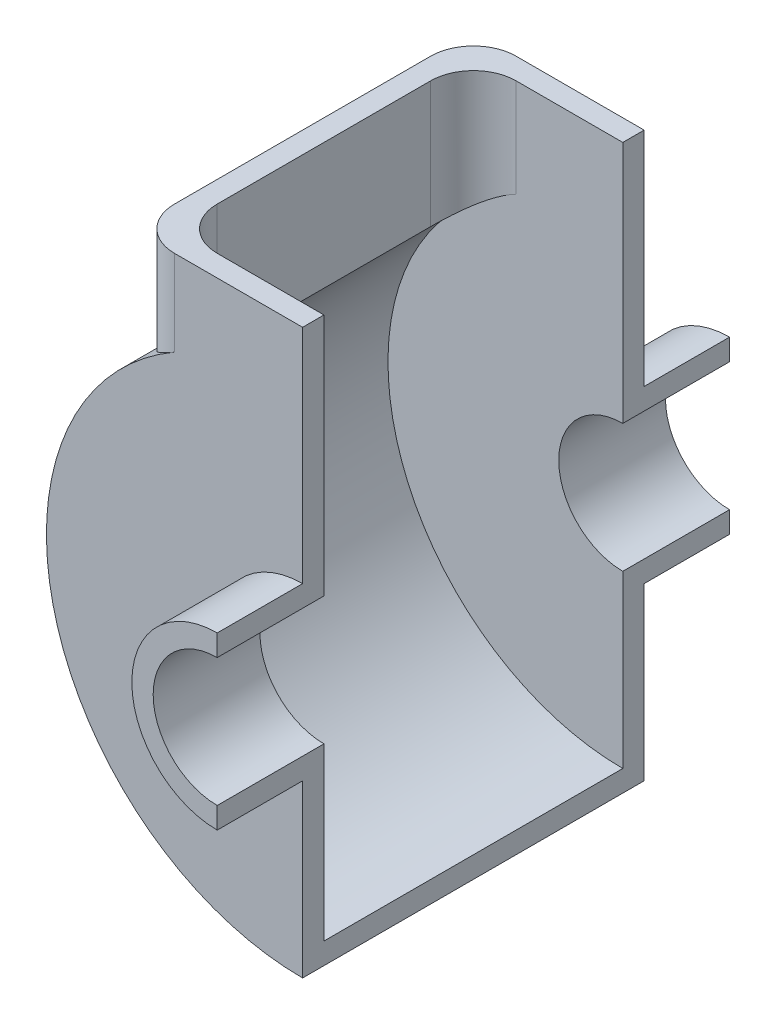
SolidWorks part; units mm, degrees
ref_plane "Płaszczyzna przednia" through (0, 0, 0) normal (0, 0, 1) x (1, 0, 0)
ref_plane "Płaszczyzna górna" through (0, 0, 0) normal (0, 1, 0) x (1, 0, 0)
ref_plane "Płaszczyzna prawa" through (0, 0, 0) normal (1, 0, 0) x (0, 0, -1)
sketch "Szkic1" plane through (0, 0, 0) normal (0, 0, 1) x (1, 0, 0)
  line L0 (0, 20) -> (0, 72)
  line L1 (0, 72) -> (-40, 72)
  line L2 (-40, 72) -> (-40, 44.7214)
  line L3 (0, 20) -> (0, 15)
  line L4 (0, -20) -> (0, -60)
  line L5 (0, -15) -> (0, -20)
  arc A0 (0, 15) -> (0, -15) centre (0, 0) ccw
  arc A1 (0, 20) -> (0, -20) centre (0, 0) ccw
  arc A2 (-40, 44.7214) -> (0, -60) centre (0, 0) ccw
  dimension "D1" = 30
  dimension "D2" = 40
  dimension "D3" = 120
  dimension "D5" = 40
  dimension "D4" = 52
extrude "Dodanie-wyciągnięcie2" add sketch "Szkic1" along normal blind 5 contours L2 A2 L4 A1 L0 L1 region at (-27.0383, 7.4311, 0)
extrude "Dodanie-wyciągnięcie3" add sketch "Szkic1<4>" along normal blind 25 contours L3 A1 L5 A0 region at (-0.4472, 17.5, 0)
sketch "Szkic1<4>" plane through (0, 0, 0) normal (0, 0, 1) x (1, 0, 0) same geometry as "Szkic1"
ref_plane "Płaszczyzna2" through (0, 0, -35) normal (0, 0, -1) x (-1, 0, 0)
ref_plane "Płaszczyzna3" through (0, 0, 0) normal (0, 0, -1) x (-1, 0, 0)
sketch "Szkic2" plane through (0, 0, 0) normal (0, 0, 1) x (1, 0, 0)
mirror "Lustro7" about plane through (0, 0, -35) normal (0, 0, -1) of bodies 103
sketch "Szkic7" plane through (0, 0, 0) normal (0, 0, 1) x (1, 0, 0)
  line L0 (-40, 72) -> (-40, 44.7214) construction
  line L1 (-40, 72) -> (-40, 44.7214)
  arc A0 (-40, 44.7214) -> (0, -60) centre (0, 0) ccw construction
  arc A1 (-40, 44.7214) -> (0, -60) centre (0, 0) ccw
sketch "Szkic8" plane through (0, 0, 0) normal (0, 0, 1) x (1, 0, 0)
  line L0 (-40, 72) -> (-40, 44.7214) construction
  line L1 (-40, 72) -> (-40, 44.7214)
  arc A0 (-40, 44.7214) -> (0, -60) centre (0, 0) ccw construction
  arc A1 (-40, 44.7214) -> (0, -60) centre (0, 0) ccw
extrude "Wyciągnięcie-cienka ścianka4" add sketch "Szkic8" against normal up to next thin thin type one direction reverse wall 5
fillet "Zaokrąglenie2" radius 10 1 edges at (-40, 58.3607, -75)
fillet "Zaokrąglenie3" radius 10 1 edges at (-40, 58.3607, 5)
fillet "Zaokrąglenie4" radius 10 1 edges at (-35, 57.2132, 0)
fillet "Zaokrąglenie5" radius 10 1 edges at (-35, 57.2132, -70)
